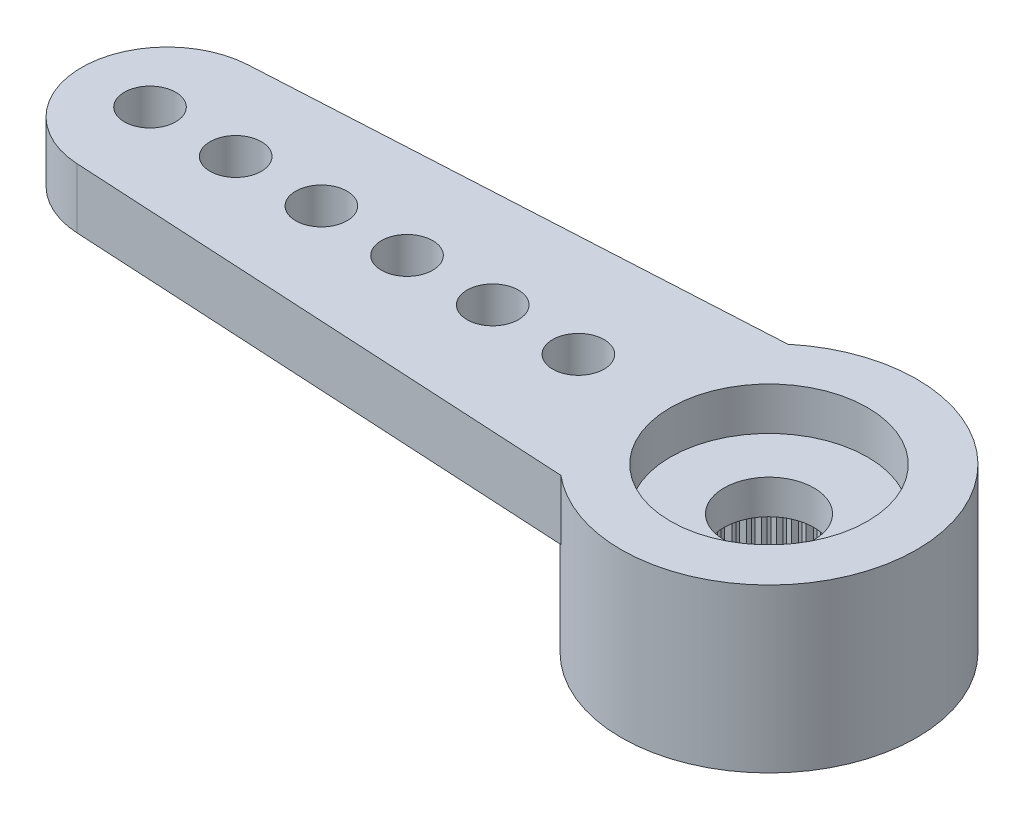
SolidWorks part; units mm, degrees
material "PVC Rígido"
ref_plane "Plano frontal" through (0, 0, 0) normal (0, 0, 1) x (1, 0, 0)
ref_plane "Plano superior" through (0, 0, 0) normal (0, 1, 0) x (1, 0, 0)
ref_plane "Plano direito" through (0, 0, 0) normal (1, 0, 0) x (0, 0, -1)
sketch "Esboço1" plane through (0, 0, 0) normal (0, 1, 0) x (1, 0, 0)
  line L0 (0, 0) -> (-14.05, 0) construction
  line L1 (-14.1591, 1.997) -> (-2.2091, 2.65)
  line L2 (-2.2091, -2.65) -> (-14.1591, -1.997)
  arc A0 (-2.2091, -2.65) -> (-2.2091, 2.65) centre (0, 0) ccw
  arc A1 (-14.1591, 1.997) -> (-14.1591, -1.997) centre (-14.05, 0) ccw
  dimension "D1" = 6.9
  dimension "D2" = 4
  dimension "D3" = 19.5
  dimension "D4" = 5.3
extrude "Ressalto-extrusão1" add sketch "Esboço1" against normal blind 1.4
sketch "Esboço2" plane through (0, -1.4, 0) normal (0, -1, 0) x (1, 0, 0)
  arc A0 (-2.2091, -2.65) -> (-2.2091, 2.65) centre (0, 0) ccw construction
  circle A1 centre (0, 0) radius 3.45
extrude "Ressalto-extrusão2" add sketch "Esboço2" along normal offset from surface (2.4 mm away) 3.8 up to face at (-7.242, 0, 0)
hole_wizard "Furo4" positions "Esboço9" profile "Esboço10" legacy end condition through all
sketch "Esboço9" plane through (0, 0, 0) normal (0, 1, 0) x (1, 0, 0)
  line L1 (-14.45, 0) -> (0, 0) construction
  arc A2 (-14.1591, 1.997) -> (-14.1591, -1.997) centre (-14.05, 0) ccw construction
  point P0 (-14.45, 0)
  point P19 (-16.05, 0)
  dimension "D1" = 1.6
sketch "Esboço10" plane through (-14.45, 0, 0) normal (1, 0, 0) x (0, 0, 1)
  line L0 (0, 0) -> (0, 3.8)
  line L1 (0, 3.8) -> (0.6, 3.8)
  line L2 (0.6, 3.8) -> (0.6, 0)
  line L3 (0.6, 0) -> (0, 0)
  line L4 (0, 110) -> (0, -10) construction
  dimension "Diameter" = 1.2
  dimension "Depth" = 3.8
pattern_linear "Padrão linear1" count 6 spacing 2 along (1, 0, 0) of "Furo4"
hole_wizard "Furo1" positions "Esboço3" profile "Esboço4" legacy
sketch "Esboço3" plane through (0, -3.8, 0) normal (0, -1, 0) x (-1, 0, 0)
  point P0 (0, 0)
sketch "Esboço4" plane through (0, -3.8, 0) normal (1, 0, 0) x (0, 0, -1)
  line L0 (0, 0) -> (0, 2)
  line L1 (0, 2) -> (2.475, 2)
  line L2 (2.475, 2) -> (2.475, 0)
  line L3 (2.475, 0) -> (0, 0)
  line L4 (0, 110) -> (0, -10) construction
  dimension "Diameter" = 4.95
  dimension "Depth" = 2
hole_wizard "Furo2" positions "Esboço5" profile "Esboço6" legacy
sketch "Esboço5" plane through (0, 0, 0) normal (0, 1, 0) x (1, 0, 0)
  point P0 (0, 0)
sketch "Esboço6" plane through (0, 0, 0) normal (1, 0, 0) x (0, 0, 1)
  line L0 (0, 0) -> (0, 1)
  line L1 (0, 1) -> (2.3, 1)
  line L2 (2.3, 1) -> (2.3, 0)
  line L3 (2.3, 0) -> (0, 0)
  line L4 (0, 110) -> (0, -10) construction
  dimension "Diameter" = 4.6
  dimension "Depth" = 1
hole_wizard "Furo3" positions "Esboço7" profile "Esboço8" legacy end condition through all
sketch "Esboço7" plane through (0, 0, 0) normal (0, 1, 0) x (1, 0, 0)
  point P0 (0, 0)
sketch "Esboço8" plane through (0, 0, 0) normal (1, 0, 0) x (0, 0, 1)
  line L0 (0, 0) -> (0, 3.8)
  line L1 (0, 3.8) -> (1.05, 3.8)
  line L2 (1.05, 3.8) -> (1.05, 0)
  line L3 (1.05, 0) -> (0, 0)
  line L4 (0, 110) -> (0, -10) construction
  dimension "Diameter" = 2.1
  dimension "Depth" = 3.8
sketch "Esboço11" plane through (0, -3.8, 0) normal (0, -1, 0) x (1, 0, 0)
  line L0 (-0.0981, 2.4731) -> (0, 2.375)
  line L1 (0, 2.375) -> (0.0981, 2.4731)
  line L2 (0, 0) -> (0, 2.475) construction
  circle A0 centre (0, 0) radius 2.375 construction
  circle A1 centre (0, 0) radius 2.475
  arc A2 (0.0981, 2.4731) -> (-0.0981, 2.4731) centre (0, 0) ccw
  dimension "D3" = 4.75
  dimension "D2" = 0.1
  dimension "D1" = 0
extrude "Ressalto-extrusão3" add sketch "Esboço11" against normal up to surface (2 mm away) up to face at (0, -1.8, 1.05)
pattern_circular "PadrãoCircular1" count 60 over 360 about axis through (0, -1.4, 0) along (0, 1, 0) of "Ressalto-extrusão3"
sketch "Sketch1" plane through (0, 0, 0) normal (0, 1, 0) x (1, 0, 0)
  line L0 (0, 0) -> (-14.45, 0)
  point P3 (-10.45, 0)
  point P4 (-12.45, 0)
  point P6 (-8.45, 0)
  point P9 (-6.45, 0)
  point P11 (-4.45, 0)
  point P15 (0, 0)
ref_axis "MOTOR_AXIS" through (0, -1, 0) along (0, 1, 0)
